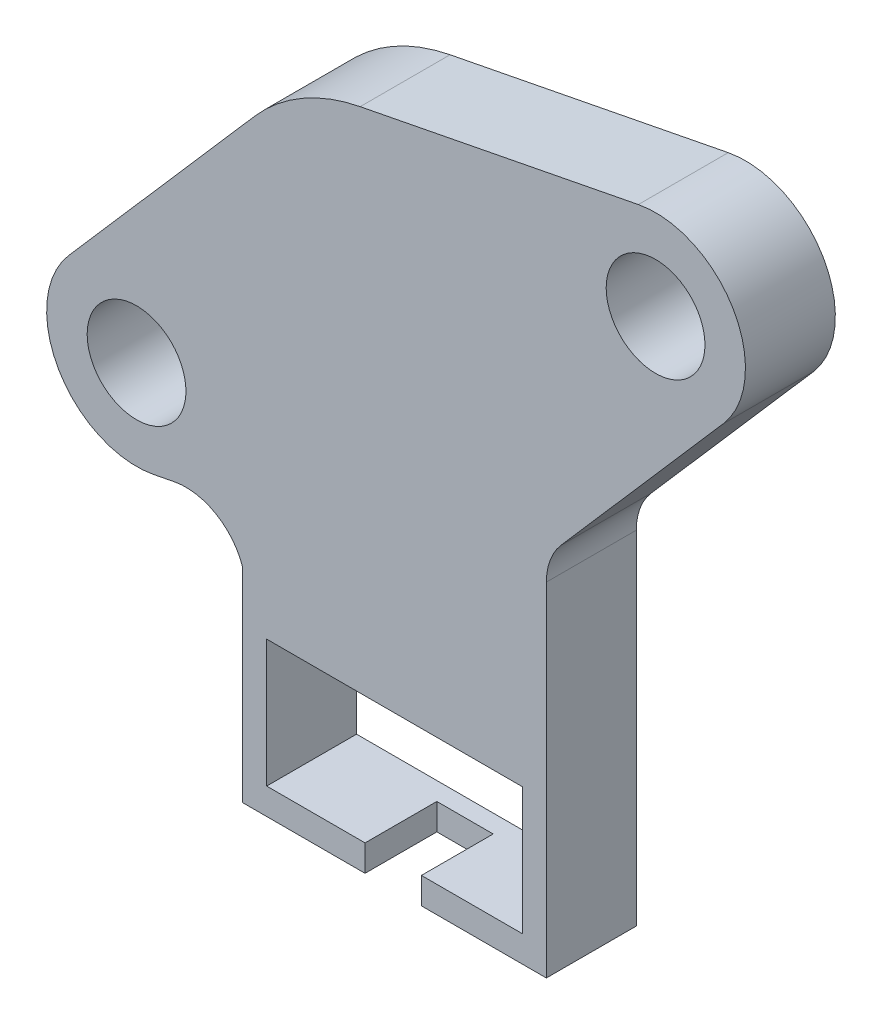
SolidWorks part; units mm, degrees
ref_plane "Front Plane" through (0, 0, 0) normal (0, 0, 1) x (1, 0, 0)
ref_plane "Top Plane" through (0, 0, 0) normal (0, 1, 0) x (1, 0, 0)
ref_plane "Right Plane" through (0, 0, 0) normal (1, 0, 0) x (0, 0, -1)
sketch "Sketch1" plane through (0, 0, 2.1073) normal (0, 0, 1) x (1, 0, 0)
  line L0 (13.3239, 2.6619) -> (0.6739, 2.6619) construction
  line L1 (0.6739, 2.6619) -> (0.6739, -2.4381) construction
  line L2 (0.6739, -2.4381) -> (13.3239, -2.4381) construction
  line L3 (13.3239, -2.4381) -> (13.3239, 2.6619) construction
  line L4 (13.6414, 2.9794) -> (0.3564, 2.9794)
  line L5 (0.3564, 2.9794) -> (0.3564, -2.7556)
  line L6 (0.3564, -2.7556) -> (13.6414, -2.7556)
  line L7 (15.111, -5.1606) -> (15.111, 13.0027)
  line L8 (15.8915, 15.0877) -> (24.488, 24.9606)
  line L9 (19.9838, 32.7623) -> (5.2476, 29.8855)
  line L10 (-0.3323, 26.6639) -> (-10.1918, 15.3404)
  line L11 (-5.6875, 7.5388) -> (-4.5981, 7.7515)
  line L12 (-0.9761, 5.6344) -> (-0.9761, -5.1606)
  line L13 (-0.9761, -5.1606) -> (15.111, -5.1606)
  line L14 (15.111, -5.1606) -> (15.111, 13.0027)
  line L15 (15.8915, 15.0877) -> (24.488, 24.9606)
  line L16 (19.9838, 32.7623) -> (5.2476, 29.8855)
  line L17 (-0.3323, 26.6639) -> (-10.1918, 15.3404)
  line L18 (-5.6875, 7.5388) -> (-4.5981, 7.7515)
  line L19 (-0.9761, 5.6344) -> (-0.9761, -5.1606)
  line L20 (-0.9761, -5.1606) -> (15.111, -5.1606)
  line L21 (13.6414, -2.7556) -> (13.6414, 2.9794)
  circle A0 centre (-6.6, 12.213) radius 2.6162 construction
  circle A1 centre (20.8963, 28.088) radius 2.6162 construction
  circle A2 centre (-6.6, 12.213) radius 2.6162
  circle A3 centre (20.8963, 28.088) radius 2.6162
  arc A5 (15.8915, 15.0877) -> (15.111, 13.0027) centre (18.286, 13.0027) ccw
  arc A6 (24.488, 24.9606) -> (19.9838, 32.7623) centre (20.8963, 28.088) ccw
  arc A7 (5.2476, 29.8855) -> (-0.3323, 26.6639) centre (7.1481, 20.1505) ccw
  arc A8 (-10.1918, 15.3404) -> (-5.6875, 7.5388) centre (-6.6, 12.213) ccw
  arc A9 (-0.9761, 5.6344) -> (-4.5981, 7.7515) centre (-3.9898, 4.6353) ccw
  arc A10 (15.8915, 15.0877) -> (15.111, 13.0027) centre (18.286, 13.0027) ccw
  arc A11 (24.488, 24.9606) -> (19.9838, 32.7623) centre (20.8963, 28.088) ccw
  arc A12 (5.2476, 29.8855) -> (-0.3323, 26.6639) centre (7.1481, 20.1505) ccw
  arc A13 (-10.1918, 15.3404) -> (-5.6875, 7.5388) centre (-6.6, 12.213) ccw
  arc A14 (-0.9761, 5.6344) -> (-4.5981, 7.7515) centre (-3.9898, 4.6353) ccw
  line M17 (13.841, -3.7636) -> (0.2939, -3.7636)
  line M18 (0.2939, -3.7636) -> (0.2939, 9.933)
  arc M19 (0.2939, 9.933) -> (-0.8698, 15.2437) centre (-12.4061, 9.933) ccw
  line M20 (-0.8698, 15.2437) -> (-0.9761, 15.4746)
  arc M21 (-0.9761, 15.4746) -> (15.111, 16.1833) centre (6.9229, 19.1109) cw
  line M22 (15.111, 16.1833) -> (14.5824, 14.7049)
  arc M23 (14.5824, 14.7049) -> (13.841, 10.4291) centre (26.541, 10.4291) ccw
  line M24 (13.841, 10.4291) -> (13.841, -3.7636)
  line M25 (15.111, -5.1606) -> (15.111, 13.0027)
  arc M26 (15.111, 13.0027) -> (15.8915, 15.0877) centre (18.286, 13.0027) cw
  line M27 (15.8915, 15.0877) -> (24.488, 24.9606)
  arc M28 (24.488, 24.9606) -> (19.9838, 32.7623) centre (20.8963, 28.088) ccw
  line M29 (19.9838, 32.7623) -> (5.2476, 29.8855)
  arc M30 (5.2476, 29.8855) -> (-0.3323, 26.6639) centre (7.1481, 20.1505) ccw
  line M31 (-0.3323, 26.6639) -> (-10.1918, 15.3404)
  arc M32 (-10.1918, 15.3404) -> (-5.6875, 7.5388) centre (-6.6, 12.213) ccw
  line M33 (-5.6875, 7.5388) -> (-4.5981, 7.7515)
  arc M34 (-4.5981, 7.7515) -> (-0.9761, 5.6344) centre (-3.9898, 4.6353) cw
  line M35 (-0.9761, 5.6344) -> (-0.9761, -5.1606)
  line M36 (-0.9761, -5.1606) -> (15.111, -5.1606)
  circle M37 centre (20.8963, 28.088) radius 2.6162
  circle M38 centre (-6.6, 12.213) radius 2.6162
  dimension "D1" = 0
  dimension "D2" = 0.3175
extrude "Boss-Extrude1" add sketch "Sketch1" along normal blind 4.7625 contours M36 M25 M26 M27 M28 M29 M30 M31 M32 M33 M34 M35 M37 M38 M24 M17 M18 M19 M20 M21 M22 M23 region at (7.0675, -4.63, 2.1073)
sketch "Sketch2" plane through (0, 0, 6.8698) normal (0, 0, 1) x (1, 0, 0)
  line L0 (0.2939, 2.9794) -> (13.841, 2.9794)
  line L1 (0.6739, 2.6619) -> (13.3239, 2.6619) construction
  line L5 (13.841, -3.7636) -> (13.841, 10.4291)
  line L6 (0.2939, -3.7636) -> (13.841, -3.7636)
  line L7 (0.2939, 9.933) -> (0.2939, -3.7636)
  line L8 (-0.9761, 15.4746) -> (-0.8698, 15.2437)
  line L9 (14.5824, 14.7049) -> (15.111, 16.1833)
  line L10 (13.841, 2.9794) -> (13.841, 10.4291)
  line L12 (0.2939, 9.933) -> (0.2939, 2.9794)
  line L13 (-0.9761, 15.4746) -> (-0.8698, 15.2437)
  line L14 (14.5824, 14.7049) -> (15.111, 16.1833)
  arc A3 (0.2939, 9.933) -> (-0.8698, 15.2437) centre (-12.4061, 9.933) ccw
  arc A4 (15.111, 16.1833) -> (-0.9761, 15.4746) centre (6.9229, 19.1109) ccw
  arc A5 (14.5824, 14.7049) -> (13.841, 10.4291) centre (26.541, 10.4291) ccw
  arc A6 (0.2939, 9.933) -> (-0.8698, 15.2437) centre (-12.4061, 9.933) ccw
  arc A7 (15.111, 16.1833) -> (-0.9761, 15.4746) centre (6.9229, 19.1109) ccw
  arc A8 (14.5824, 14.7049) -> (13.841, 10.4291) centre (26.541, 10.4291) ccw
  point P11 (0, 0)
  point P16 (0, 0)
  dimension "D2" = 0.3175
  dimension "D1" = 0
extrude "Boss-Extrude2" add sketch "Sketch2" against normal blind 3.81
sketch "Sketch3" plane through (0, -5.1606, 0) normal (0, -1, 0) x (1, 0, 0)
  line L0 (5.8239, 3.3851) -> (5.8239, 6.8851) construction
  line L1 (8.1739, 6.8851) -> (8.1739, 3.3851) construction
  line L2 (5.8239, 3.3851) -> (5.8239, 6.8851) construction
  line L3 (8.1739, 6.8851) -> (8.1739, 3.3851) construction
  line L4 (5.8239, 3.3851) -> (8.1739, 3.3851) construction
  line L5 (8.4914, 6.8851) -> (8.4914, 3.0676)
  line L6 (5.5064, 3.0676) -> (8.4914, 3.0676)
  line L7 (5.5064, 3.0676) -> (5.5064, 6.8851)
  line M9 (15.111, 6.8698) -> (-0.9761, 6.8698)
  dimension "D1" = 0.3175
extrude "Cut-Extrude1" cut sketch "Sketch3" against normal blind 1.524 and the other way through all contours L7 L6 L5 M9 region at (6.9989, -5.1606, 4.9687)
